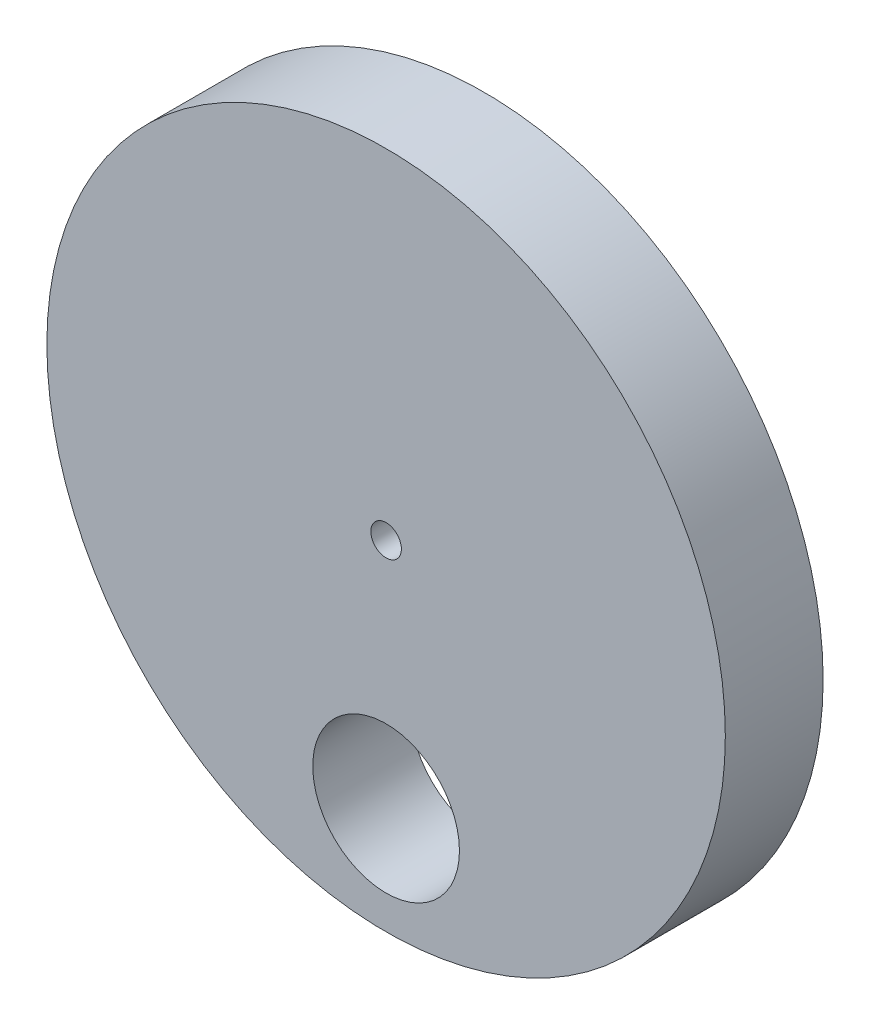
SolidWorks part; units mm, degrees
ref_plane "Front" through (0, 0, 0) normal (0, 0, 1) x (1, 0, 0)
ref_plane "Top" through (0, 0, 0) normal (0, 1, 0) x (1, 0, 0)
ref_plane "Right" through (0, 0, 0) normal (1, 0, 0) x (0, 0, -1)
ref_axis "Center Axis" through (0, 0, -0.35) along (0, 0, 1)
sketch "Sketch1" plane through (0, 0, 0) normal (0, 0, 1) x (1, 0, 0)
  circle A0 centre (0, 0) radius 55.5
  dimension "D1" = 111
extrude "Boss-Extrude1" add sketch "Sketch1" along normal blind 16
sketch "Sketch2" plane through (0, 0, 16) normal (0, 0, 1) x (1, 0, 0)
  circle A0 centre (0, -38) radius 12
  dimension "D1" = 24
  dimension "D2" = 38
extrude "Cut-Extrude1" cut sketch "Sketch2" against normal blind 16
sketch "Sketch3" plane through (0, 0, 16) normal (0, 0, 1) x (1, 0, 0)
  circle A0 centre (0, 0) radius 2.5
  dimension "D1" = 5
extrude "Cut-Extrude2" cut sketch "Sketch3" against normal blind 16
shell "Shell2" thickness 3.1 removed face at (2.5, 0, 0)
